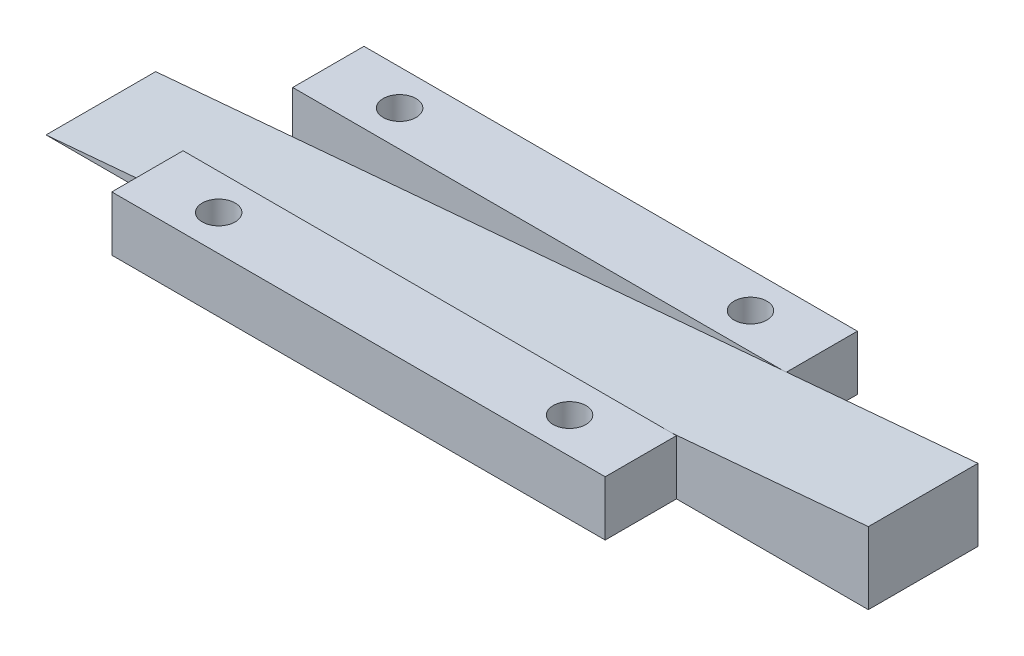
SolidWorks part; units mm, degrees
ref_plane "Front Plane" through (0, 0, 0) normal (0, 0, 1) x (1, 0, 0)
ref_plane "Top Plane" through (0, 0, 0) normal (0, 1, 0) x (1, 0, 0)
ref_plane "Right Plane" through (0, 0, 0) normal (1, 0, 0) x (0, 0, -1)
sketch "Sketch1" plane through (0, 0, 0) normal (0, 0, 1) x (1, 0, 0)
  line L0 (-104.4564, 0) -> (45.5436, 0)
  line L1 (55, 0) -> (-55, 0) construction
  line L2 (45.5436, 0) -> (45.5436, 13.1233)
  line L3 (45.5436, 13.1233) -> (-104.4564, 0)
  dimension "D1" = 150
  dimension "D2" = 5
extrude "Boss-Extrude1" add sketch "Sketch1" along normal mid plane 20
sketch "Sketch2" plane through (0, 0, 10) normal (0, 0, 1) x (1, 0, 0)
  line L0 (10.5436, 10) -> (10.5436, 0)
  line L1 (10.5436, 10) -> (-79.4564, 10)
  line L2 (10.5436, 0) -> (-79.4564, 0)
  line L3 (-79.4564, 10) -> (-79.4564, 0)
  line L6 (45.5436, 0) -> (45.5436, 13.1233) construction
  point P8 (0, 0)
  point P9 (0, 0)
  dimension "D1" = 10
  dimension "D2" = 35
  dimension "D3" = 90
sketch "Sketch3" plane through (0, 0, -10) normal (0, 0, 1) x (1, 0, 0)
  line L0 (10.5436, 10) -> (10.5436, 0)
  line L1 (10.5436, 10) -> (-79.4564, 10)
  line L2 (10.5436, 0) -> (-79.4564, 0)
  line L3 (-79.4564, 10) -> (-79.4564, 0)
  line L6 (45.5436, 0) -> (45.5436, 13.1233) construction
  point P0 (0, 0)
  dimension "D1" = 10
  dimension "D2" = 35
  dimension "D3" = 90
extrude "Boss-Extrude2" add sketch "Sketch2" along normal blind 13
extrude "Boss-Extrude3" add sketch "Sketch3" against normal blind 13
sketch "Sketch5" plane through (0, 10, -10) normal (0, -1, 0) x (1, 0, 0)
  line L0 (-66.4564, -6.5) -> (-66.4564, 26.5) construction
  line L1 (-66.4564, 26.5) -> (-2.4564, 26.5) construction
  line L2 (-2.4564, 26.5) -> (-2.4564, -6.5) construction
  line L3 (-2.4564, -6.5) -> (-66.4564, -6.5) construction
  line L8 (-79.4564, 33) -> (10.5436, 33) construction
  line L9 (-79.4564, -13) -> (-79.4564, 0) construction
  line L11 (-79.4564, -13) -> (10.5436, -13) construction
  line L12 (10.5436, 33) -> (10.5436, 20) construction
  circle A0 centre (-66.4564, 26.5) radius 3
  circle A1 centre (-2.4564, 26.5) radius 3
  circle A2 centre (-2.4564, -6.5) radius 3
  circle A3 centre (-66.4564, -6.5) radius 3
  dimension "D1" = 6
  dimension "D2" = 6.5
  dimension "D3" = 13
  dimension "D4" = 13
  dimension "D5" = 6.5
extrude "Cut-Extrude2" cut sketch "Sketch5" along direction (0, -1, 0) on the side of the normal blind 13
